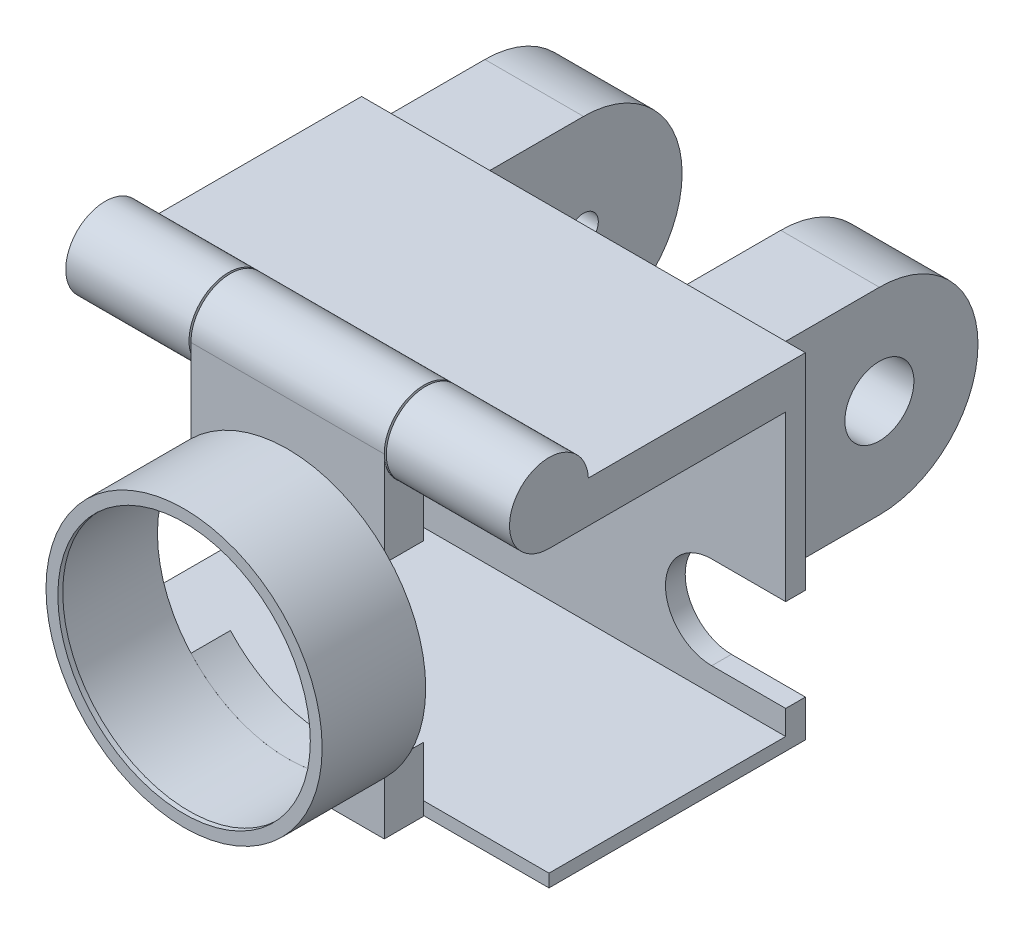
SolidWorks part; units mm, degrees
ref_plane "前基準面" through (0, 0, 0) normal (0, 0, 1) x (1, 0, 0)
ref_plane "上基準面" through (0, 0, 0) normal (0, 1, 0) x (1, 0, 0)
ref_plane "右基準面" through (0, 0, 0) normal (1, 0, 0) x (0, 0, -1)
sketch "草圖1" plane through (0, 0, 0) normal (0, 0, 1) x (1, 0, 0)
  line L1 (-22.5, -17) -> (22.5, -17)
  line L2 (-22.5, -17) -> (-22.5, 17)
  line L3 (-22.5, 17) -> (22.5, 17)
  line L4 (22.5, -17) -> (22.5, 17)
  line L5 (-22.5, -17) -> (22.5, 17) construction
  line L6 (-22.5, 17) -> (22.5, -17) construction
  point P0 (0, 0)
  dimension "D1" = 45
  dimension "D2" = 34
extrude "填料-伸長1" add sketch "草圖1" against normal blind 2
sketch "草圖2" plane through (0, 0, -2) normal (0, 0, -1) x (-1, 0, 0)
  line L0 (-10, 16.5) -> (10, 16.5) construction
  line L1 (-10, 16.5) -> (-20, 16.5)
  line L2 (10, 16.5) -> (20, 16.5)
  line L3 (-20, 16.5) -> (-20, -3.5)
  line L4 (20, 16.5) -> (20, -3.5)
  line L5 (-20, -3.5) -> (-10, -3.5)
  line L6 (-10, -3.5) -> (-10, 16.5)
  line L7 (10, 16.5) -> (10, -3.5)
  line L8 (22.5, 17) -> (-22.5, 17) construction
  line L9 (10, -3.5) -> (20, -3.5)
  point P2 (0, 16.5)
  dimension "D1" = 10
  dimension "D2" = 20
  dimension "D3" = 10
  dimension "D4" = 20
  dimension "D5" = 20
  dimension "D6" = 10
  dimension "D7" = 0.5
extrude "填料-伸長2" add sketch "草圖2" along normal blind 20
fillet "圓角1" radius 10 4 edges at (-15, 16.5, -22) (-15, -3.5, -22) (15, -3.5, -22) (15, 16.5, -22)
sketch "草圖3" plane through (20, 0, 0) normal (1, 0, 0) x (0, 0, -1)
  line L0 (12, 16.5) -> (12, 6.5) construction
  circle A0 centre (12, 6.5) radius 3.5
extrude "除料-伸長1" cut sketch "草圖3" against normal blind 5
sketch "草圖4" plane through (-20, 0, 0) normal (-1, 0, 0) x (0, 0, 1)
  line L0 (-12, 16.5) -> (-12, 6.5) construction
  line L1 (-22, 6.5) -> (-12, 6.5) construction
  circle A0 centre (-12, 6.5) radius 3.5
extrude "除料-伸長2" cut sketch "草圖4" against normal blind 5
sketch "草圖5" plane through (15, 0, 0) normal (1, 0, 0) x (0, 0, -1)
  circle A0 centre (12, 6.5) radius 1.5
extrude "除料-伸長3" cut sketch "草圖5" against normal blind 30
sketch "草圖6" plane through (0, 0, -2) normal (0, 0, -1) x (-1, 0, 0)
  line L0 (-15, -3.8602) -> (-15, -13.2357)
  line L1 (-15, -3.5) -> (-15, -3.8602) construction
  line L4 (-20, -3.5) -> (-10, -3.5) construction
  line L6 (-22.5, -17) -> (-22.5, 17) construction
  line L7 (-15, -3.8602) -> (-22.5, -3.8602)
  line L8 (-15, -3.8602) -> (-15, -13.2357)
  line L9 (-15, -13.2357) -> (-22.5, -13.2357)
  line L10 (-22.5, -3.8602) -> (-22.5, -13.2357)
  arc A2 (-15, -3.8602) -> (-15, -13.2357) centre (-15, -8.548) cw
  line M6 (-22.5, 17) -> (-22.5, -17)
extrude "除料-伸長4" cut sketch "草圖6" against normal blind 2 contours L0 | L9 L0 L7 M6 region at (13.0105, -8.548, -2) region at (18.75, -8.548, -2)
sketch "草圖7" plane through (0, 0, 0) normal (0, 0, 1) x (1, 0, 0)
  line L0 (22.5, -17) -> (22.5, 17) construction
  line L1 (-22.5, -17) -> (22.5, -17)
  line L2 (-22.5, -17) -> (-22.5, -15.7)
  line L3 (-22.5, -15.7) -> (22.5, -15.7)
  line L4 (22.5, -17) -> (22.5, -15.7)
  dimension "D1" = 1.3
extrude "填料-伸長3" add sketch "草圖7" along normal blind 24
sketch "草圖9" plane through (0, 0, 0) normal (0, 0, 1) x (1, 0, 0)
  line L0 (22.5, -17) -> (22.5, 17) construction
  line L1 (-22.5, 17) -> (22.5, 17)
  line L2 (-22.5, 17) -> (-22.5, 12.8)
  line L3 (-22.5, 12.8) -> (22.5, 12.8)
  line L4 (22.5, 17) -> (22.5, 12.8)
  dimension "D1" = 4.2
extrude "填料-伸長4" add sketch "草圖9" along normal blind 20
ref_plane "平面1" through (22.5, 0, 0) normal (1, 0, 0) x (0, 0, -1)
sketch "草圖10" plane through (22.5, 0, 0) normal (1, 0, 0) x (0, 0, -1)
  line L0 (-20, 12.8) -> (-24, 12.8) construction
  line L1 (-20, 12.8) -> (-20, 17) construction
  circle A0 centre (-24, 16.8) radius 4
  dimension "D1" = 4
extrude "填料-伸長7" add sketch "草圖10" against normal blind 45
ref_plane "平面2" through (10, 0, 0) normal (1, 0, 0) x (0, 0, -1)
sketch "草圖15" plane through (10, 0, 0) normal (1, 0, 0) x (0, 0, -1)
  circle A0 centre (-24, 16.8) radius 4
extrude "除料-伸長10" cut sketch "草圖15" against normal blind 20
sketch "草圖16" plane through (22.5, 0, 0) normal (1, 0, 0) x (0, 0, -1)
  line L0 (-24, 12.8) -> (-20, 12.8)
  line L1 (-20, 12.8) -> (-20, 16.8)
  line L2 (-20, 12.8) -> (-20, 17) construction
  circle A0 centre (-24, 16.8) radius 4 construction
  arc A1 (-20, 16.8) -> (-24, 12.8) centre (-24, 16.8) cw
extrude "填料-伸長14" add sketch "草圖16" against normal blind 45
ref_plane "平面3" through (9.8, 0, 0) normal (1, 0, 0) x (0, 0, -1)
sketch "草圖18" plane through (9.8, 0, 0) normal (1, 0, 0) x (0, 0, -1)
  circle A0 centre (-24, 16.8) radius 4
extrude "填料-伸長16" add sketch "草圖18" against normal blind 19.6
sketch "草圖20" plane through (9.8, 0, 0) normal (1, 0, 0) x (0, 0, -1)
  line L0 (-20, 16.8) -> (-20, 12.8)
  line L1 (-24, 12.8) -> (0, 12.8) construction
  line L2 (-20, 12.8) -> (-24, 12.8)
  arc A0 (-20, 16.8) -> (-24, 12.8) centre (-24, 16.8) cw
extrude "除料-伸長11" cut sketch "草圖20" against normal blind 19.6
sketch "草圖21" plane through (9.8, 0, 0) normal (1, 0, 0) x (0, 0, -1)
  line L0 (-24, 12.8) -> (-24, -16.2)
  line L1 (-24, -16.2) -> (-20, -16.2)
  line L2 (-20, -16.2) -> (-20, 16.8)
  arc A0 (-24, 12.8) -> (-20, 16.8) centre (-24, 16.8) ccw
  dimension "D1" = 4
sketch "草圖25" plane through (22.5, 0, 0) normal (1, 0, 0) x (0, 0, -1)
  circle A0 centre (-24, 16.8) radius 3.5
  point P3 (0, 0)
sketch "草圖26" plane through (-22.5, 0, 0) normal (-1, 0, 0) x (0, 0, 1)
  circle A0 centre (24, 16.8) radius 3.5
sketch "草圖28" plane through (9.8, 0, 0) normal (1, 0, 0) x (0, 0, -1)
  line L0 (-27.9997, 16.75) -> (-27.9997, -17.05)
  line L1 (-24, 12.8) -> (-24, -17.05)
  line L2 (-24, -17.05) -> (-27.9997, -17.05)
  arc A0 (-20, 16.8) -> (-24, 12.8) centre (-24, 16.8) ccw construction
  arc A1 (-27.9997, 16.75) -> (-24, 12.8) centre (-24.0494, 16.75) ccw
  point P7 (-24, 12.8)
  dimension "D1" = 33.8
  dimension "D2" = 29.85
  dimension "D3" = 3.9997
extrude "填料-伸長22" add sketch "草圖28" against normal blind 19.6
sketch "草圖29" plane through (0, 0, 27.9997) normal (0, 0, 1) x (1, 0, 0)
  line L0 (0, 12.8) -> (0, -1.7) construction
  line L1 (9.8, 12.8) -> (0, 12.8) construction
  line L2 (9.8, 12.8) -> (9.8, -16.2) construction
  line L3 (0, 12.8) -> (-9.8, 12.8) construction
  line L4 (-9.8, 16.75) -> (-9.8, -17.05) construction
  circle A0 centre (0, -1.7) radius 14
  dimension "D1" = 14.5
extrude "填料-伸長23" add sketch "草圖29" along normal blind 10.5
sketch "草圖30" plane through (0, 0, 24) normal (0, 0, -1) x (-1, 0, 0)
  circle A0 centre (0, -1.7) radius 13.2
extrude "除料-伸長17" cut sketch "草圖30" against normal blind 4
sketch "草圖31" plane through (0, 0, 38.4997) normal (0, 0, 1) x (1, 0, 0)
  circle A0 centre (0, -1.7) radius 12.8
extrude "除料-伸長18" cut sketch "草圖31" against normal blind 0.5
sketch "草圖32" plane through (0, 0, 27.9997) normal (0, 0, -1) x (-1, 0, 0)
  circle A0 centre (0, -1.7) radius 13.2
extrude "除料-伸長19" cut sketch "草圖32" against normal blind 10
